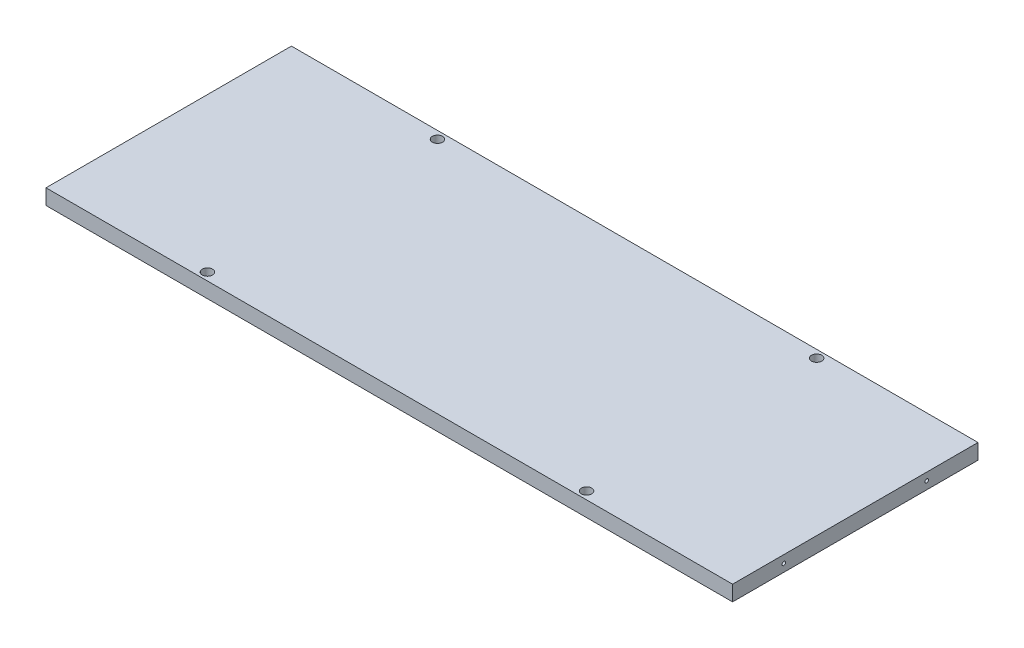
SolidWorks part; units mm, degrees
ref_plane "前视基准面" through (0, 0, 0) normal (0, 0, 1) x (1, 0, 0)
ref_plane "上视基准面" through (0, 0, 0) normal (0, 1, 0) x (1, 0, 0)
ref_plane "右视基准面" through (0, 0, 0) normal (1, 0, 0) x (0, 0, -1)
other "Configuration Table"
sketch "草图1" plane through (0, 0, 0) normal (0, 0, 1) x (1, 0, 0)
  line L61 (-67, 1.5) -> (67, 1.5)
  line L62 (-67, 1.5) -> (-67, -1.5)
  line L63 (-67, -1.5) -> (67, -1.5)
  line L64 (67, 1.5) -> (67, -1.5)
  point P4 (0, 1.5)
  point P5 (-67, 0)
  dimension "D1" = 3
  dimension "D2" = 134
extrude "凸台-拉伸1" add sketch "草图1" along normal blind 47.9
sketch "草图4" plane through (0, 1.5, 0) normal (0, 1, 0) x (1, 0, 0)
  line L0 (-37, -46.4) -> (37, -46.4)
  line L1 (-67, -47.9) -> (-67, 0) construction
  line L2 (67, -47.9) -> (-67, -47.9) construction
  line L3 (-37, -1.5) -> (37, -1.5)
  line L4 (67, 0) -> (-67, 0) construction
  circle A0 centre (-37, -46.4) radius 0.7
  circle A1 centre (37, -46.4) radius 0.7
  circle A2 centre (-37, -46.4) radius 1
  circle A3 centre (37, -46.4) radius 1
  circle A4 centre (-37, -1.5) radius 0.7
  circle A5 centre (37, -1.5) radius 0.7
  circle A6 centre (37, -1.5) radius 1
  circle A7 centre (-37, -1.5) radius 1
  point P6 (0, -46.4)
  dimension "D1" = 1.4
  dimension "D2" = 2
  dimension "D3" = 30
  dimension "D4" = 1.5
  dimension "D5" = 1.5
extrude "切除-拉伸1" cut sketch "草图4" against normal through all contours A1 | A0 | A4 | A5
extrude "切除-拉伸2" cut sketch "草图4<3>" against normal blind 1.5 contours A2 | A3 | A7 | A6
sketch "草图4<3>" plane through (0, 1.5, 0) normal (0, 1, 0) x (1, 0, 0) same geometry as "草图4"
sketch "草图5" plane through (0, -1.5, 0) normal (0, -1, 0) x (1, 0, 0)
  circle A0 centre (-42.3, 22.35) radius 0.35
  circle A1 centre (42.3, 22.35) radius 0.35
  point P6 (0, 0)
  point P7 (0, 0)
  dimension "D1" = 0.7
extrude "切除-拉伸3" cut sketch "草图5" against normal blind 1.5 contours A0 | A1
sketch "草图6" plane through (67, 0, 0) normal (1, 0, 0) x (0, 0, -1)
  line L0 (-37.9, 0) -> (-47.9, 0)
  line L1 (-47.9, -1.5) -> (-47.9, 1.5) construction
  line L2 (-10, 0) -> (0, 0)
  circle A0 centre (-37.9, 0) radius 0.35
  circle A1 centre (-10, 0) radius 0.35
  dimension "D1" = 0.7
  dimension "D2" = 10
extrude "切除-拉伸4" cut sketch "草图6" against normal blind 1.5 contours A0 | A1
extrude "切除-拉伸5" cut sketch "草图6<3>" along normal blind 1.5 from surface contours A1 | A0 starting at face at (-67, 0, 23.95)
sketch "草图6<3>" plane through (67, 0, 0) normal (1, 0, 0) x (0, 0, -1) same geometry as "草图6"
